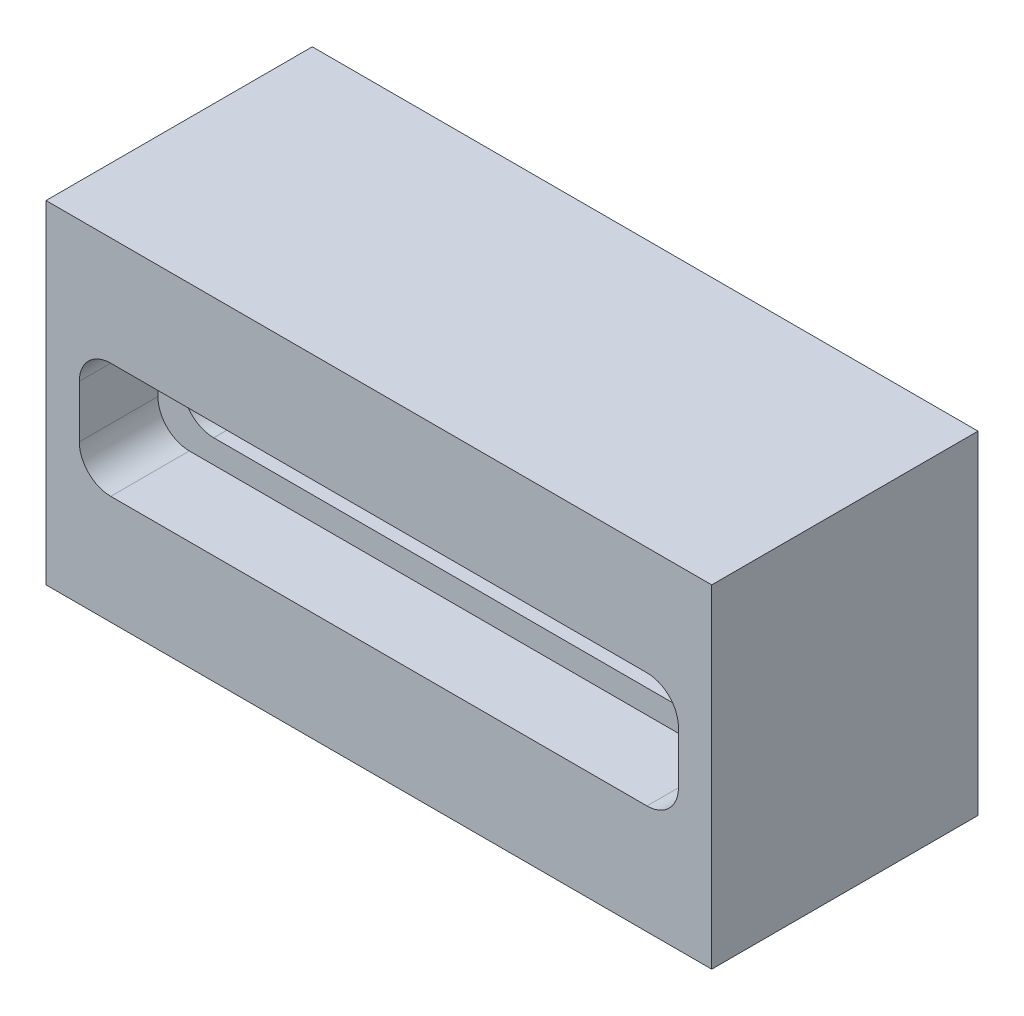
SolidWorks part; units mm, degrees
ref_plane "Front Plane" through (0, 0, 0) normal (0, 0, 1) x (1, 0, 0)
ref_plane "Top Plane" through (0, 0, 0) normal (0, 1, 0) x (1, 0, 0)
ref_plane "Right Plane" through (0, 0, 0) normal (1, 0, 0) x (0, 0, -1)
sketch "Sketch1" plane through (0, 0, 0) normal (0, 1, 0) x (1, 0, 0)
  line L1 (0, 0) -> (127, 0)
  line L2 (0, 0) -> (0, 50.8)
  line L3 (0, 50.8) -> (127, 50.8)
  line L4 (127, 0) -> (127, 50.8)
  dimension "D1" = 50.8
  dimension "D2" = 127
extrude "Boss-Extrude1" add sketch "Sketch1" along normal blind 63.5
sketch "Sketch2" plane through (0, 0, 0) normal (0, 0, 1) x (1, 0, 0)
  line L1 (0, 0) -> (63.5, 0)
  line L2 (0, 0) -> (0, 31.8)
  line L3 (0, 31.8) -> (63.5, 31.8)
  line L4 (63.5, 0) -> (63.5, 31.8)
  line L5 (17, 38.3) -> (110, 38.3)
  line L6 (11, 32.3) -> (11, 31.3)
  line L7 (17, 25.3) -> (110, 25.3)
  line L8 (116, 32.3) -> (116, 31.3)
  line L9 (11, 38.3) -> (116, 25.3) construction
  line L10 (11, 25.3) -> (116, 38.3) construction
  arc A0 (110, 38.3) -> (116, 32.3) centre (110, 32.3) cw
  arc A1 (110, 25.3) -> (116, 31.3) centre (110, 31.3) ccw
  arc A2 (11, 31.3) -> (17, 25.3) centre (17, 31.3) ccw
  arc A3 (17, 38.3) -> (11, 32.3) centre (17, 32.3) ccw
  dimension "D5" = 6
  dimension "D1" = 31.8
  dimension "D2" = 63.5
  dimension "D3" = 105
  dimension "D4" = 13
sketch "Sketch3" plane through (0, 0, 0) normal (0, 0, 1) x (1, 0, 0)
  line L1 (0, 0) -> (63.5, 0)
  line L2 (0, 0) -> (0, 31.8)
  line L3 (0, 31.8) -> (63.5, 31.8)
  line L4 (63.5, 0) -> (63.5, 31.8)
  line L5 (12.35, 42.8) -> (114.65, 42.8)
  line L6 (6.35, 36.8) -> (6.35, 26.8)
  line L7 (12.35, 20.8) -> (114.65, 20.8)
  line L8 (120.65, 36.8) -> (120.65, 26.8)
  line L9 (6.35, 42.8) -> (120.65, 20.8) construction
  line L10 (6.35, 20.8) -> (120.65, 42.8) construction
  arc A0 (12.35, 42.8) -> (6.35, 36.8) centre (12.35, 36.8) ccw
  arc A1 (6.35, 26.8) -> (12.35, 20.8) centre (12.35, 26.8) ccw
  arc A2 (114.65, 20.8) -> (120.65, 26.8) centre (114.65, 26.8) ccw
  arc A3 (114.65, 42.8) -> (120.65, 36.8) centre (114.65, 36.8) cw
  dimension "D4" = 6
  dimension "D1" = 63.5
  dimension "D2" = 31.8
  dimension "D3" = 114.3
  dimension "D5" = 10
extrude "Cut-Extrude2" cut sketch "Sketch3" against normal blind 15 contours L5 A3 L8 A2 L7 A1 L6 A0
extrude "Cut-Extrude3" cut sketch "Sketch2" against normal through all contours L5 A0 L8 A1 L7 A2 L6 A3
